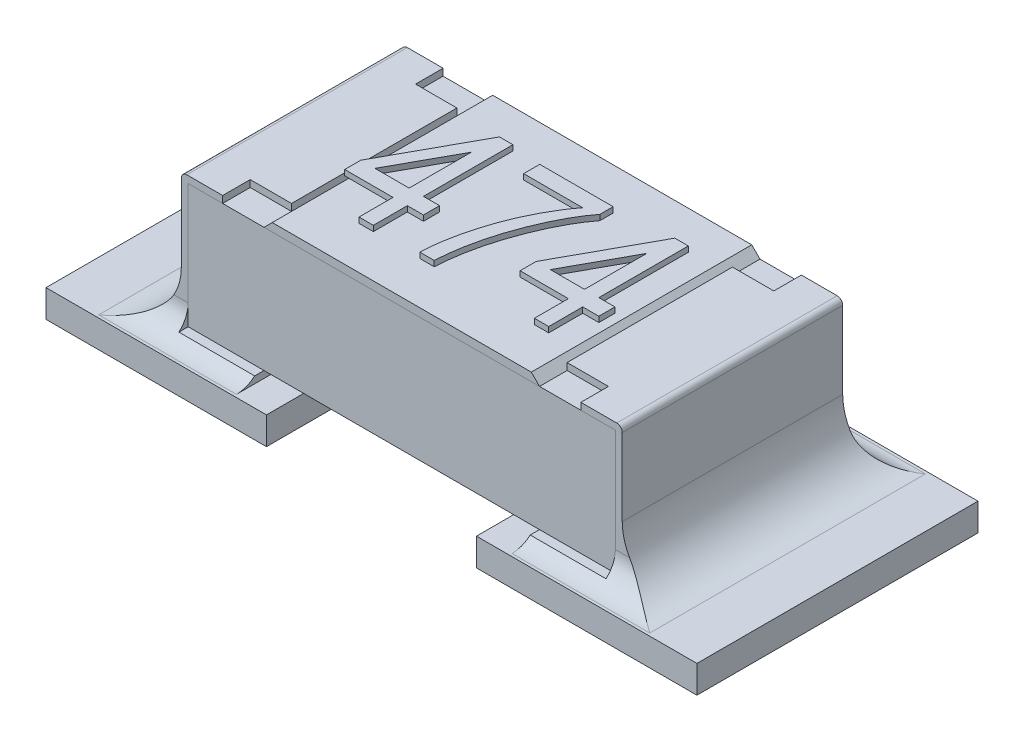
SolidWorks part; units mm, degrees
material "Ceramic Porcelain"
ref_plane "Front Plane" through (0, 0, 0) normal (0, 0, 1) x (1, 0, 0)
ref_plane "Top Plane" through (0, 0, 0) normal (0, 1, 0) x (1, 0, 0)
ref_plane "Right Plane" through (0, 0, 0) normal (1, 0, 0) x (0, 0, -1)
sketch "Sketch1" plane through (0, 0, 0) normal (1, 0, 0) x (0, 0, -1)
  line L0 (0, 55) -> (0, -55) construction
  line L1 (-0.4, 0.575) -> (0.4, 0.575)
  line L2 (-0.4, 0.575) -> (-0.4, 0.125)
  line L3 (-0.4, 0.125) -> (0.4, 0.125)
  line L4 (0.4, 0.575) -> (0.4, 0.125)
  line L5 (55, 0) -> (-55, 0) construction
  dimension "D1" = 0.8
  dimension "D2" = 0.4
  dimension "D3" = 0.45
  dimension "D4" = 0.125
extrude "Boss-Extrude1" add sketch "Sketch1" along normal mid plane 1.55
sketch "Sketch2" plane through (0, 0, 0) normal (0, 0, 1) x (1, 0, 0)
  line L0 (-0.5, 0.6) -> (-0.78, 0.6)
  line L1 (-0.8, 0.58) -> (-0.8, 0.1)
  line L2 (-0.8, 0.1) -> (-0.5, 0.1)
  line L3 (-0.5, 0.1) -> (-0.5, 0.125)
  line L4 (0.775, 0.125) -> (-0.775, 0.125) construction
  line L5 (-0.5, 0.125) -> (-0.775, 0.125)
  line L6 (-0.775, 0.125) -> (-0.775, 0.575)
  line L7 (-0.775, 0.575) -> (-0.5, 0.575)
  line L8 (0.775, 0.575) -> (-0.775, 0.575) construction
  line L9 (-0.5, 0.575) -> (-0.5, 0.6)
  line L11 (0.5, 0.575) -> (0.5, 0.6)
  line L12 (0.5, 0.6) -> (0.78, 0.6)
  line L13 (0.8, 0.58) -> (0.8, 0.1)
  line L14 (0.8, 0.1) -> (0.5, 0.1)
  line L15 (0.5, 0.1) -> (0.5, 0.125)
  line L16 (0.5, 0.125) -> (0.775, 0.125)
  line L17 (0.775, 0.125) -> (0.775, 0.575)
  line L18 (0.775, 0.575) -> (0.5, 0.575)
  arc A0 (0.78, 0.6) -> (0.8, 0.58) centre (0.78, 0.58) cw
  arc A1 (-0.78, 0.6) -> (-0.8, 0.58) centre (-0.78, 0.58) ccw
  point P28 (-0.8, 0.6)
  dimension "D6" = 0.02
  dimension "D1" = 0.025
  dimension "D2" = 0.025
  dimension "D3" = 0.025
  dimension "D4" = 0.3
  dimension "D5" = 0.3
extrude "Boss-Extrude2" add sketch "Sketch2" along normal mid plane 0.8 separate body
sketch "Sketch3" plane through (0, 0.6, 0) normal (0, 1, 0) x (1, 0, 0)
  line L0 (0.5, -0.4) -> (0.5, 0.4) construction
  line L1 (-0.5, 0.4) -> (-0.65, 0.4)
  line L2 (-0.5, 0.4) -> (-0.5, 0.3)
  line L3 (-0.5, 0.3) -> (-0.65, 0.3)
  line L4 (-0.65, 0.4) -> (-0.65, 0.3)
  line L5 (-0.5, -0.4) -> (-0.65, -0.4)
  line L6 (-0.5, -0.4) -> (-0.5, -0.3)
  line L7 (-0.5, -0.3) -> (-0.65, -0.3)
  line L8 (-0.65, -0.4) -> (-0.65, -0.3)
  line L9 (0.5, -0.4) -> (0.65, -0.4)
  line L10 (0.5, -0.4) -> (0.5, -0.3)
  line L11 (0.5, -0.3) -> (0.65, -0.3)
  line L12 (0.65, -0.4) -> (0.65, -0.3)
  line L13 (0.775, -0.4) -> (-0.775, -0.4) construction
  line L15 (0.5, 0.4) -> (0.65, 0.4)
  line L16 (0.5, 0.4) -> (0.5, 0.3)
  line L17 (0.5, 0.3) -> (0.65, 0.3)
  line L18 (0.65, 0.4) -> (0.65, 0.3)
  dimension "D1" = 0.15
  dimension "D2" = 0.1
extrude "Cut-Extrude1" cut sketch "Sketch3" against normal blind 0.025
sketch "Sketch4" plane through (0, 0, 0) normal (0, 0, 1) x (1, 0, 0)
  line L0 (-0.5, 0.575) -> (0.5, 0.575)
  line L1 (0.5, 0.575) -> (0.47, 0.605)
  line L2 (0.47, 0.605) -> (-0.47, 0.605)
  line L3 (-0.47, 0.605) -> (-0.5, 0.575)
  dimension "D1" = 45
  dimension "D2" = 45
  dimension "D3" = 0.03
extrude "Boss-Extrude3" add sketch "Sketch4" along normal mid plane 0.8 separate body
sketch "Sketch7" plane through (0, 0, 0) normal (0, 1, 0) x (1, 0, 0)
  line L0 (0, -0.2833) -> (0, 0.2833) construction
  line L1 (-0.381, -0.51) -> (-1.181, -0.51)
  line L2 (-0.381, -0.51) -> (-0.381, 0.51)
  line L3 (-0.381, 0.51) -> (-1.181, 0.51)
  line L4 (-1.181, -0.51) -> (-1.181, 0.51)
  line L5 (0.381, -0.51) -> (1.181, -0.51)
  line L6 (0.381, -0.51) -> (0.381, 0.51)
  line L7 (0.381, 0.51) -> (1.181, 0.51)
  line L8 (1.181, -0.51) -> (1.181, 0.51)
  line L9 (-0.2833, 0) -> (0.2833, 0) construction
  dimension "D1" = 0.8
  dimension "D2" = 0.381
  dimension "D3" = 0.381
  dimension "D4" = 1.02
  dimension "D5" = 0.51
extrude "Boss-Extrude5" add sketch "Sketch7" along normal blind 0.1
fillet "Fillet3" radius 0.2 1 edges at (-0.8, 0.1, 0)
fillet "Fillet4" radius 0.2 1 edges at (0.8, 0.1, 0)
fillet "Fillet5" radius 0.1 2 edges at (0.75, 0.1, -0.4) (0.75, 0.1, 0.4)
fillet "Fillet6" radius 0.1 2 edges at (-0.75, 0.1, 0.4) (-0.75, 0.1, -0.4)
sketch "Esquisse2" plane through (0, 0.605, 0) normal (0, 1, 0) x (1, 0, 0)
  text T0 "474" font "Arial Narrow" height 0.5
extrude "Boss.-Extru.1" add sketch "Esquisse2" along normal blind 0.02
